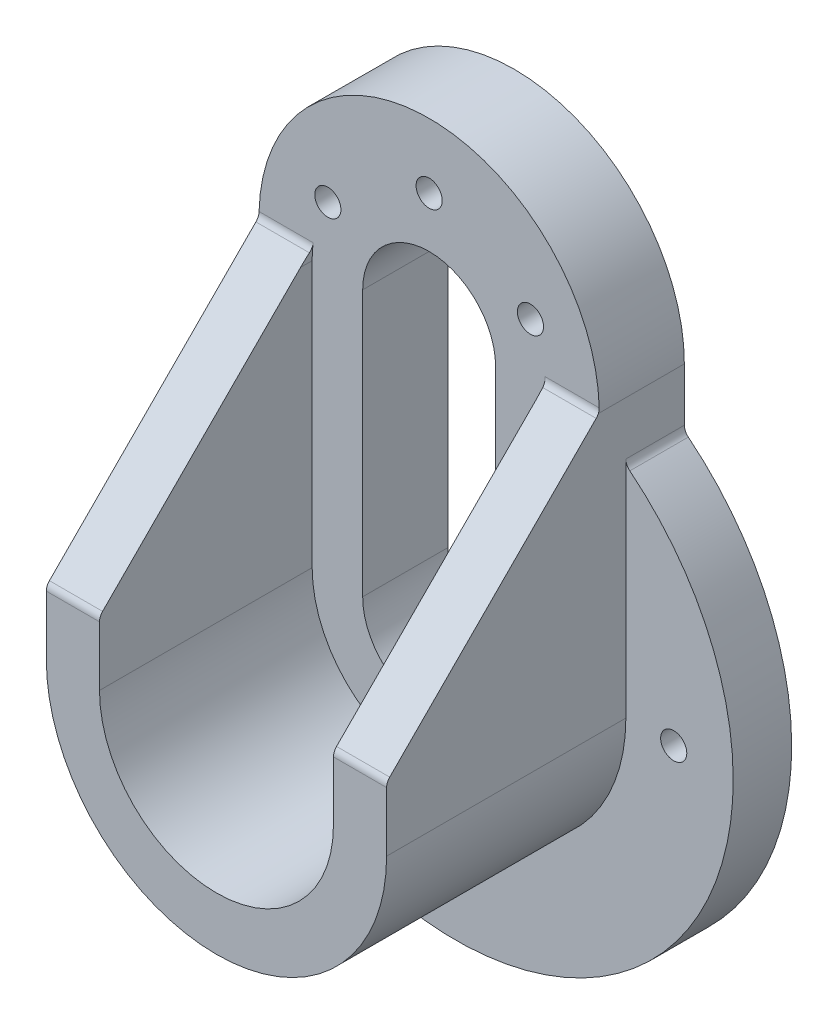
SolidWorks part; units mm, degrees
ref_plane "Front Plane" through (0, 0, 0) normal (0, 0, 1) x (1, 0, 0)
ref_plane "Top Plane" through (0, 0, 0) normal (0, 1, 0) x (1, 0, 0)
ref_plane "Right Plane" through (0, 0, 0) normal (1, 0, 0) x (0, 0, -1)
sketch "Sketch1" plane through (0, 0, 0) normal (0, 0, 1) x (1, 0, 0)
  line L0 (0, 0) -> (0, 52.1878) construction
  line L1 (-32, 0) -> (-32, 52.1878)
  line L2 (32, 0) -> (32, 52.1878)
  arc A0 (-32, 0) -> (32, 0) centre (0, 0) ccw
  arc A1 (32, 52.1878) -> (-32, 52.1878) centre (0, 52.1878) ccw
  circle A2 centre (0, 0) radius 52.1878
  point P3 (0, 26.0939)
  dimension "D1" = 32
  dimension "D2" = 104.3757
extrude "Boss-Extrude1" add sketch "Sketch1" against normal blind 16 and the other way blind 40 contours L2 A2 L1 A0 | A2 L2 A1 L1 region at (0, 11.5092, 0) region at (0, 63.723, 0)
extrude "Boss-Extrude2" add sketch "Sketch1<3>" against normal blind 11 from offset 5 contours A2 offset against normal yes
sketch "Sketch1<3>" plane through (0, 0, 0) normal (0, 0, 1) x (1, 0, 0) same geometry as "Sketch1"
sketch "Sketch2" plane through (0, 0, 40) normal (0, 0, 1) x (1, 0, 0)
  line L0 (0, 0) -> (0, 50) construction
  line L1 (-12.5, 0) -> (-12.5, 50)
  line L2 (12.5, 0) -> (12.5, 50)
  arc A0 (-12.5, 0) -> (12.5, 0) centre (0, 0) ccw
  arc A1 (12.5, 50) -> (-12.5, 50) centre (0, 50) ccw
  point P3 (0, 25)
  dimension "D1" = 12.5
  dimension "D2" = 25
extrude "Cut-Extrude1" cut sketch "Sketch2" against normal through all
sketch "Sketch6" plane through (0, 0, 40) normal (0, 0, 1) x (1, 0, 0)
  line L0 (0, 0) -> (0, 50) construction
  line L1 (-22, 0) -> (-22, 50)
  line L2 (22, 0) -> (22, 50)
  arc A0 (-22, 0) -> (22, 0) centre (0, 0) ccw
  arc A1 (22, 50) -> (-22, 50) centre (0, 50) ccw
  point P3 (0, 25)
  dimension "D1" = 22
  dimension "D2" = 25
extrude "Cut-Extrude3" cut sketch "Sketch6" against normal blind 40
sketch "Sketch7" plane through (32, 0, 0) normal (1, 0, 0) x (0, 0, -1)
  line L1 (-40, 0) -> (-40, 52.1878) construction
  line L2 (0, 52.1878) -> (0, 84.1878)
  line L3 (-40, 52.1878) -> (16, 52.1878) construction
  line L4 (0, 52.1878) -> (-40, 12)
  line L5 (16, 84.1878) -> (-40, 84.1878) construction
  line L6 (0, 84.1878) -> (-40, 84.1878)
  line L7 (-40, 84.1878) -> (-40, 52.1878) construction
  line L8 (-40, 84.1878) -> (-40, 12)
  line L9 (5, 41.2258) -> (16, 41.2258) construction
  dimension "D1" = 29.2258
extrude "Cut-Extrude4" cut sketch "Sketch7" against normal through all
fillet "Fillet1" radius 2 2 edges at (27, 12, 40) (-27, 12, 40)
sketch "Sketch12" plane through (0, 0, 0) normal (0, 0, 1) x (1, 0, 0)
  line L0 (0, 72) -> (0, 50) construction
  line L1 (0, 50) -> (19.0526, 61) construction
  line L2 (0, 50) -> (-19.0526, 61) construction
  line L4 (-32, 52.1878) -> (-21.8909, 52.1878) construction
  circle A0 centre (0, 50) radius 22
  circle A1 centre (0, 72) radius 4.9149
  dimension "D1" = 9.8298
  dimension "D2" = 44
  dimension "D3" = 8.8122
hole_wizard "#10 (0.1935) Diameter Hole3" positions "Sketch22" profile "Sketch23" hole size "#10" standard "ANSI Inch" end condition through all
sketch "Sketch22" plane through (0, 0, 0) normal (0, 0, 1) x (1, 0, 0)
  point P0 (-19.0526, 61)
  point P3 (19.0526, 61)
  point P7 (0, 72)
sketch "Sketch23" plane through (-19.0526, 61, 0) normal (1, 0, 0) x (0, -1, 0)
  line L0 (0, 0) -> (0, 16)
  line L1 (0, 16) -> (2.4574, 16)
  line L2 (2.4574, 16) -> (2.4574, 0)
  line L5 (2.4574, 0) -> (0, 0)
  line L11 (0, -6.35) -> (0, 107.95) construction
  dimension "Thru Hole Dia." = 4.9149
  dimension "Thru Hole Depth" = 16
sketch "Sketch28" plane through (0, 0, -16) normal (0, 0, -1) x (-1, 0, 0)
  circle A0 centre (0, 0) radius 41
  dimension "D1" = 82
hole_wizard "#10 (0.1935) Diameter Hole4" positions "Sketch29" profile "Sketch30" hole size "#10" standard "ANSI Inch" end condition through all
sketch "Sketch29" plane through (0, 0, -16) normal (0, 0, -1) x (-1, 0, 0)
  line L0 (-12.5, 0) -> (-12.5, 50) construction
  circle A0 centre (0, 0) radius 41 construction
  point P0 (0, -41)
  point P4 (41, 0)
  point P6 (-41, 0)
  dimension "D1" = 12.5
sketch "Sketch30" plane through (0, -41, -16) normal (1, 0, 0) x (0, 1, 0)
  line L0 (0, 0) -> (0, 56)
  line L1 (0, 56) -> (2.4574, 56)
  line L2 (2.4574, 56) -> (2.4574, 0)
  line L5 (2.4574, 0) -> (0, 0)
  line L11 (0, -6.35) -> (0, 107.95) construction
  dimension "Thru Hole Dia." = 4.9149
  dimension "Thru Hole Depth" = 56
fillet "Fillet2" radius 2 2 edges at (26.9455, 52.1878, 0) (-26.9455, 52.1878, 0)
fillet "Fillet3" radius 2 2 edges at (-32, 41.2258, -10.5) (32, 41.2258, -10.5)
